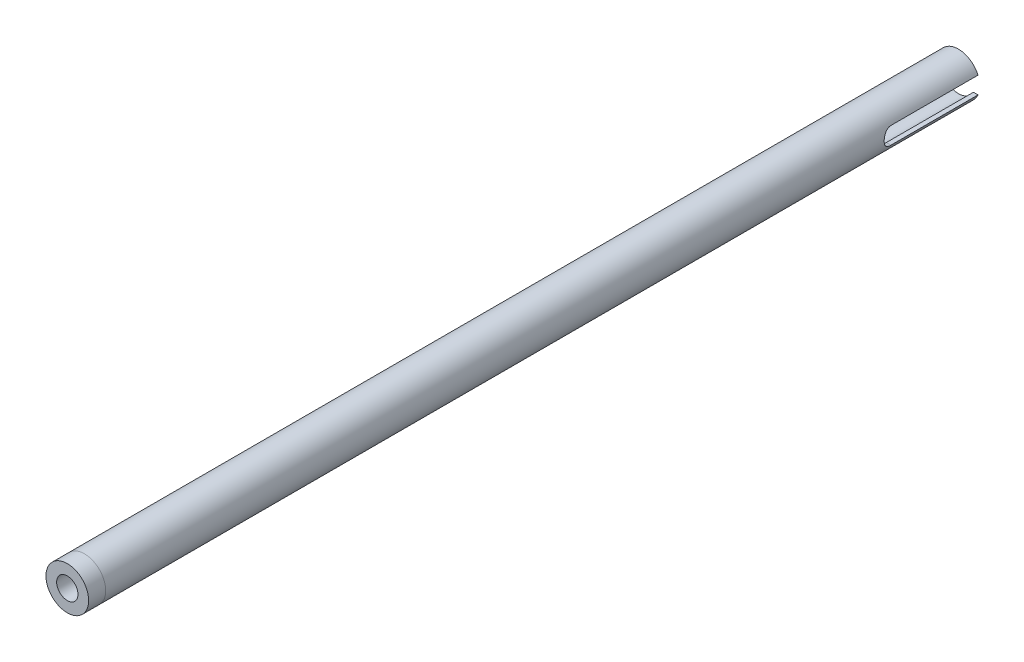
SolidWorks part; units mm, degrees
ref_plane "Front Plane" through (0, 0, 0) normal (0, 0, 1) x (1, 0, 0)
ref_plane "Top Plane" through (0, 0, 0) normal (0, 1, 0) x (1, 0, 0)
ref_plane "Right Plane" through (0, 0, 0) normal (1, 0, 0) x (0, 0, -1)
sketch "Axis" plane through (0, 0, 0) normal (0, 1, 0) x (1, 0, 0)
  line L0 (0, 0) -> (0, 331.464) construction
  line L1 (0, 0) -> (0, -28.575) construction
  line L2 (0, 331.464) -> (-7.9375, 331.464) construction
  line L3 (0, 360.8328) -> (-10.3187, 322.6534) construction
  dimension "D1" = 28.575
  dimension "D2" = 7.9375
sketch "Sketch1" plane through (0, 0, 0) normal (0, 0, 1) x (1, 0, 0)
  line L0 (-7.9375, 0) -> (7.9375, 0) construction
  line L1 (-7.2748, 3.175) -> (7.2748, 3.175)
  line L2 (-7.2748, -3.175) -> (7.2748, -3.175)
  circle A0 centre (0, 0) radius 7.9375
  circle A1 centre (0, 0) radius 6.4135
  circle A2 centre (0, 0) radius 3.9688
  dimension "D1" = 15.875
  dimension "D3" = 7.9375
  dimension "D2" = 1.524
  dimension "D4" = 6.35
extrude "Threaded insert 1-1" add sketch "Sketch1" against normal blind 6.35 contours A2 L1 A1 | A1 L1 A0 | A2 L0 A1 L1 | A1 L0 A0 L1 | L0 A1 L2 A0 | L0 A2 L2 A1 | A2 L2 A1 | A1 L2 A0 | L0 A1 L2 A2 | L0 A0 L2 A1 | A0 L0 A1 L1 | A1 L0 A2 L1 region at (4.7887, 1.6543, 0) region at (4.7887, -1.6543, 0) region at (6.9234, 1.6163, 0) region at (6.9234, -1.6163, 0) region at (-4.7887, -1.6543, 0) region at (-4.7887, 1.6543, 0) region at (0, 4.6159, 0) region at (0, -4.6159, 0) region at (0, 6.5666, 0) region at (6.4237, -3.3281, 0) region at (-6.9234, -1.6163, 0) region at (-6.9234, 1.6163, 0)
extrude "Threaded insert 1-2" add sketch "Sketch1<3>" against normal blind 9.525 from surface contours A2 L1 A1 | A2 L0 A1 L1 | L0 A2 L2 A1 | A2 L2 A1 | L0 A1 L2 A2 | A1 L0 A2 L1 region at (4.7887, 1.6543, 0) region at (4.7887, -1.6543, 0) region at (-4.7887, -1.6543, 0) region at (-4.7887, 1.6543, 0) region at (0, 4.6159, 0) region at (0, -4.6159, 0) starting at face at (7.9375, 0, -6.35)
sketch "Sketch1<3>" plane through (0, 0, 0) normal (0, 0, 1) x (1, 0, 0) same geometry as "Sketch1"
extrude "A-arm tube" add sketch "Sketch1<4>" against normal up to vertex (331.464 mm away) from surface separate body contours A1 L1 A0 | A1 L0 A0 L1 | L0 A1 L2 A0 | A1 L2 A0 | L0 A0 L2 A1 | A0 L0 A1 L1 region at (6.9234, 1.6163, 0) region at (6.9234, -1.6163, 0) region at (0, 6.5666, 0) region at (6.4237, -3.3281, 0) region at (-6.9234, -1.6163, 0) region at (-6.9234, 1.6163, 0) up to point (0, 0, -331.464) starting at face at (6.4135, 0, -6.35)
sketch "Sketch1<4>" plane through (0, 0, 0) normal (0, 0, 1) x (1, 0, 0) same geometry as "Sketch1"
extrude "Apex slot" cut sketch "Sketch1<5>" along normal blind 35.56 from surface contours A0 L0 A1 L1 | L0 A0 L2 A1 | A1 L0 A0 L1 | L0 A1 L2 A0 region at (6.9234, 1.6163, 0) region at (6.9234, -1.6163, 0) region at (-6.9234, -1.6163, 0) region at (-6.9234, 1.6163, 0) starting at face at (6.4135, 0, -331.464)
sketch "Sketch1<5>" plane through (0, 0, 0) normal (0, 0, 1) x (1, 0, 0) same geometry as "Sketch1"
fillet "Fillet1" radius 3.175 4 edges at (-6.4237, 3.175, -295.904) (-6.4237, -3.175, -295.904) (6.4237, -3.175, -295.904) (6.4237, 3.175, -295.904)
equation "\"tube diameter\"= 5 / 8"
equation "\"tube thickness\"= .06"
equation "\"apex thickness\"= .25"
equation "\"tube slot\"= 1.4"
equation "\"D1@Sketch1\"=\"tube diameter\""
equation "\"D2@Sketch1\"=\"tube thickness\""
equation "\"threaded insert hole\"= .3125"
equation "\"D3@Sketch1\"=\"threaded insert hole\""
equation "\"D4@Sketch1\"=\"apex thickness\""
equation "\"D1@Apex slot\" = \"tube slot\""
equation "\"D1@Fillet1\"=\"apex thickness\"/2"
equation "\"D2@Axis\"=\"tube diameter\"/2"
